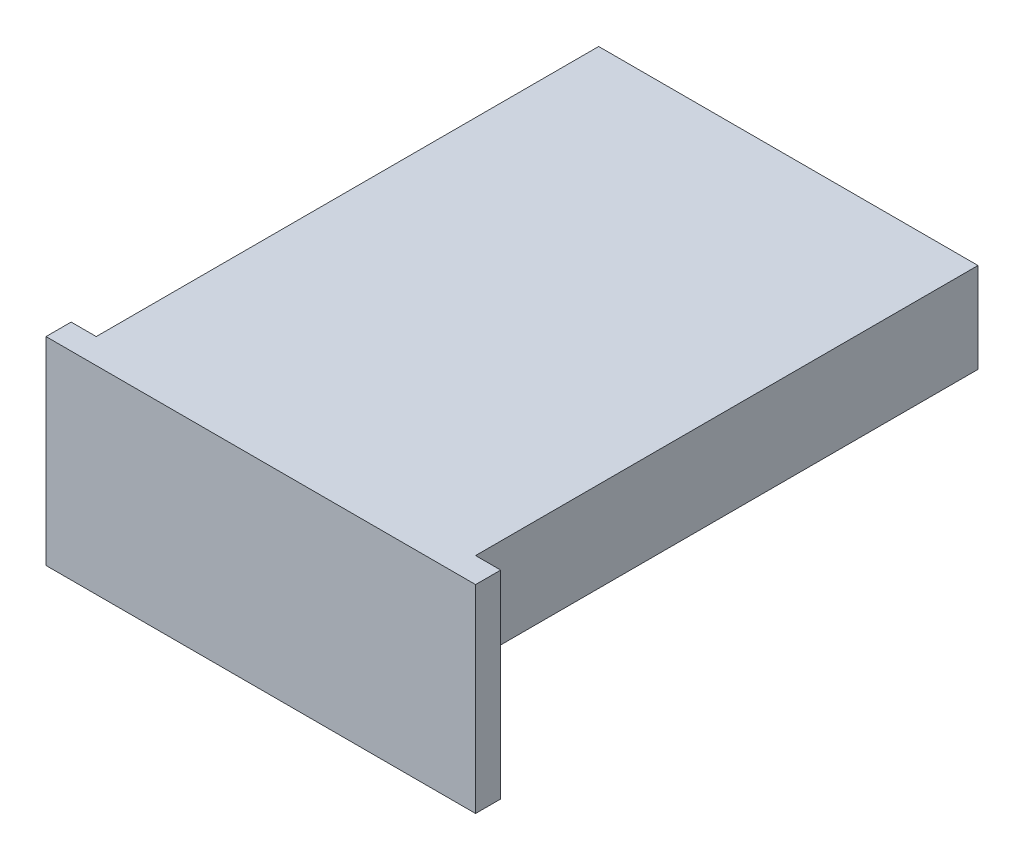
SolidWorks part; units mm, degrees
ref_plane "Front Plane" through (0, 0, 0) normal (0, 0, 1) x (1, 0, 0)
ref_plane "Top Plane" through (0, 0, 0) normal (0, 1, 0) x (1, 0, 0)
ref_plane "Right Plane" through (0, 0, 0) normal (1, 0, 0) x (0, 0, -1)
sketch "Sketch1" plane through (0, -22.4385, -0.0002) normal (0, 1, 0) x (1, 0, 0)
  line L4 (80.038, 6.103) -> (78.038, 6.103)
  line L5 (80.038, 6.103) -> (78.038, 6.103)
  line L6 (78.038, 26.103) -> (62.938, 26.103)
  line L7 (78.038, 26.103) -> (62.938, 26.103)
  line L14 (78.038, 6.103) -> (78.038, 26.103)
  line L15 (78.038, 6.103) -> (78.038, 26.103)
  line L16 (62.938, 26.103) -> (62.938, 6.103)
  line L17 (62.938, 26.103) -> (62.938, 6.103)
  line L79 (62.938, 6.103) -> (60.5428, 6.103)
  line L80 (62.938, 6.103) -> (60.5428, 6.103)
  line L81 (146.4404, 6.103) -> (146.4404, 26.103)
  line L82 (146.4404, 6.103) -> (146.4404, 26.103)
  line L83 (146.4404, 26.103) -> (131.338, 26.103)
  line L84 (146.4404, 26.103) -> (131.338, 26.103)
  line L85 (131.338, 26.103) -> (131.338, 6.103)
  line L86 (131.338, 26.103) -> (131.338, 6.103)
  line L87 (131.338, 6.103) -> (129.338, 6.103)
  line L88 (131.338, 6.103) -> (129.338, 6.103)
  line L89 (129.338, 6.103) -> (129.338, 26.103)
  line L90 (129.338, 6.103) -> (129.338, 26.103)
  line L91 (129.338, 26.103) -> (114.238, 26.103)
  line L92 (129.338, 26.103) -> (114.238, 26.103)
  line L93 (114.238, 26.103) -> (114.238, 6.103)
  line L94 (114.238, 26.103) -> (114.238, 6.103)
  line L95 (114.238, 6.103) -> (112.238, 6.103)
  line L96 (114.238, 6.103) -> (112.238, 6.103)
  line L97 (112.238, 6.103) -> (112.238, 26.103)
  line L98 (112.238, 6.103) -> (112.238, 26.103)
  line L99 (112.238, 26.103) -> (97.138, 26.103)
  line L100 (112.238, 26.103) -> (97.138, 26.103)
  line L101 (97.138, 26.103) -> (97.138, 6.103)
  line L102 (97.138, 26.103) -> (97.138, 6.103)
  line L103 (97.138, 6.103) -> (95.138, 6.103)
  line L104 (97.138, 6.103) -> (95.138, 6.103)
  line L105 (95.138, 6.103) -> (95.138, 26.103)
  line L106 (95.138, 6.103) -> (95.138, 26.103)
  line L107 (95.138, 26.103) -> (80.038, 26.103)
  line L108 (95.138, 26.103) -> (80.038, 26.103)
  line L109 (80.038, 26.103) -> (80.038, 6.103)
  line L110 (80.038, 26.103) -> (80.038, 6.103)
  line L111 (149.0321, 6.103) -> (146.4404, 6.103)
  line L112 (149.0321, 6.103) -> (146.4404, 6.103)
  arc A1 (60.5428, 6.103) -> (60.5959, 6.0115) centre (73.6219, 13.6322) ccw
  arc A2 (60.5428, 6.103) -> (60.5959, 6.0115) centre (73.6219, 13.6322) ccw
  spline S3 degree 3 poles (1817.8665, 957.8692) (-1812.7007, -801.1687) (1972.7377, 742.4675) (-1779.9076, -773.9188) knots -29.662381 -29.662381 -29.662381 -29.662381 32.998383 32.998383 32.998383 32.998383 only from (61.1644, 5.1151) to (62.5644, 3.3076)
  spline S4 degree 3 poles (548.8295, -1936.4915) (68.1721, 117.1489) (41.7438, 23.7507) (63.9834, 1.8165) (64.3645, 1.4758) (65.5511, 0.508) (66.3975, -0.0681) (68.1618, -1.131) (69.0656, -1.6129) (70.9072, -2.4757) (71.8473, -2.8546) (73.758, -3.5302) (74.728, -3.8283) (76.6807, -4.3902) (77.6629, -4.6553) (79.6355, -5.163) (80.6269, -5.4019) (82.6154, -5.8388) (83.6137, -6.0359) (85.6141, -6.4083) (86.6163, -6.584) (88.622, -6.928) (89.6256, -7.0959) (92.6392, -7.5851) (94.6533, -7.8906) (97.6787, -8.2804) (98.6882, -8.3974) (100.712, -8.5681) (101.7263, -8.6231) (103.759, -8.6779) (104.7772, -8.6815) (106.8164, -8.6518) (107.8346, -8.6197) (109.8636, -8.4895) (110.8742, -8.3881) (112.8914, -8.1479) (113.898, -8.0094) (116.9153, -7.5695) (118.9237, -7.2381) (121.9279, -6.7189) (122.9282, -6.542) (124.9259, -6.1777) (125.9229, -5.9891) (127.9067, -5.5749) (128.8931, -5.3485) (130.8559, -4.8592) (131.8333, -4.6003) (133.7815, -4.0591) (134.7528, -3.7785) (136.6775, -3.1531) (137.6304, -2.8065) (139.0374, -2.2069) (139.5031, -1.9951) (140.4295, -1.554) (140.891, -1.3271) (141.8041, -0.8385) (142.2585, -0.5733) (143.1225, 0.0059) (143.536, 0.3177) (144.1477, 0.7954) (144.3502, 0.9564) (144.7554, 1.2781) (144.9578, 1.4391) (162.9576, 16.0958) (166.0883, 48.1369) (-1083.6442, 1578.9651) knots -0.820445 -0.820445 -0.820445 -0.820445 0.115071 0.115071 0.130696 0.130696 0.161946 0.161946 0.193196 0.193196 0.224446 0.224446 0.255696 0.255696 0.286946 0.286946 0.318196 0.318196 0.349446 0.349446 0.380696 0.380696 0.411946 0.411946 0.474446 0.474446 0.505696 0.505696 0.536946 0.536946 0.568196 0.568196 0.599446 0.599446 0.630696 0.630696 0.661946 0.661946 0.724446 0.724446 0.755696 0.755696 0.786946 0.786946 0.818196 0.818196 0.849446 0.849446 0.880696 0.880696 0.911946 0.911946 0.927571 0.927571 0.943196 0.943196 0.958821 0.958821 0.974446 0.974446 0.982259 0.982259 0.990071 0.990071 1.683487 1.683487 1.683487 1.683487 only from (62.5644, 3.3076) to (145.9103, 2.2401)
  spline S6 degree 3 poles (61.1644, 5.1151) (61.5972, 4.4806) (62.0704, 3.8809) (62.5644, 3.3076) knots 0 0 0 0 0.685452 0.685452 0.685452 0.685452 construction
  spline S7 degree 3 poles (62.5644, 3.3076) (62.9009, 2.9175) (63.2527, 2.5372) (63.9834, 1.8165) (64.3645, 1.4758) (65.5511, 0.508) (66.3975, -0.0681) (68.1618, -1.131) (69.0656, -1.6129) (70.9072, -2.4757) (71.8473, -2.8546) (73.758, -3.5302) (74.728, -3.8283) (76.6807, -4.3902) (77.6629, -4.6553) (79.6355, -5.163) (80.6269, -5.4019) (82.6154, -5.8388) (83.6137, -6.0359) (85.6141, -6.4083) (86.6163, -6.584) (88.622, -6.928) (89.6256, -7.0959) (92.6392, -7.5851) (94.6533, -7.8906) (97.6787, -8.2804) (98.6882, -8.3974) (100.712, -8.5681) (101.7263, -8.6231) (103.759, -8.6779) (104.7772, -8.6815) (106.8164, -8.6518) (107.8346, -8.6197) (109.8636, -8.4895) (110.8742, -8.3881) (112.8914, -8.1479) (113.898, -8.0094) (116.9153, -7.5695) (118.9237, -7.2381) (121.9279, -6.7189) (122.9282, -6.542) (124.9259, -6.1777) (125.9229, -5.9891) (127.9067, -5.5749) (128.8931, -5.3485) (130.8559, -4.8592) (131.8333, -4.6003) (133.7815, -4.0591) (134.7528, -3.7785) (136.6775, -3.1531) (137.6304, -2.8065) (139.0374, -2.2069) (139.5031, -1.9951) (140.4295, -1.554) (140.891, -1.3271) (141.8041, -0.8385) (142.2585, -0.5733) (143.1225, 0.0059) (143.536, 0.3177) (144.1477, 0.7954) (144.3502, 0.9564) (144.7554, 1.2781) (144.9578, 1.4391) (145.4132, 1.8099) (145.6651, 2.021) (145.9103, 2.2401) knots 0.099446 0.099446 0.099446 0.099446 0.115071 0.115071 0.130696 0.130696 0.161946 0.161946 0.193196 0.193196 0.224446 0.224446 0.255696 0.255696 0.286946 0.286946 0.318196 0.318196 0.349446 0.349446 0.380696 0.380696 0.411946 0.411946 0.474446 0.474446 0.505696 0.505696 0.536946 0.536946 0.568196 0.568196 0.599446 0.599446 0.630696 0.630696 0.661946 0.661946 0.724446 0.724446 0.755696 0.755696 0.786946 0.786946 0.818196 0.818196 0.849446 0.849446 0.880696 0.880696 0.911946 0.911946 0.927571 0.927571 0.943196 0.943196 0.958821 0.958821 0.974446 0.974446 0.982259 0.982259 0.990071 0.990071 1 1 1 1 construction
  spline S16 degree 3 poles (1372.6595, -1576.7465) (65.1848, 24.8122) (129.0525, -14.1517) (146.6971, 2.9872) (147.0468, 3.3764) (147.7131, 4.1895) (148.0276, 4.6072) (165.4719, 29.2726) (129.935, 85.2105) (-1517.3371, 1110.9512) knots -0.67008 -0.67008 -0.67008 -0.67008 0.055384 0.055384 0.071009 0.071009 0.086634 0.086634 0.976126 0.976126 0.976126 0.976126 only from (145.9103, 2.2401) to (149.0321, 6.103)
  spline S17 degree 3 poles (145.9103, 2.2401) (146.0509, 2.3658) (146.1894, 2.4941) (146.6971, 2.9872) (147.0468, 3.3764) (147.7131, 4.1895) (148.0276, 4.6072) (148.5757, 5.3822) (148.8117, 5.7379) (149.0321, 6.103) knots 0.049688 0.049688 0.049688 0.049688 0.055384 0.055384 0.071009 0.071009 0.086634 0.086634 0.099446 0.099446 0.099446 0.099446
  spline S46 degree 3 poles (1817.9148, 957.8926) (-1812.905, -801.2651) (1973.1102, 742.6193) (-1780.4368, -774.1326) knots -28.662659 -28.662659 -28.662659 -28.662659 34.001328 34.001328 34.001328 34.001328 only from (60.5959, 6.0115) to (61.1644, 5.1151)
  spline S47 degree 3 poles (60.5959, 6.0115) (60.7756, 5.7048) (60.9657, 5.4063) (61.1644, 5.1151) knots 0.685452 0.685452 0.685452 0.685452 1 1 1 1
  dimension "D1" = 0
sketch "Sketch3" plane through (0, 0.0002, -26.103) normal (0, 0, 1) x (1, 0, 0)
  line L1 (97.138, 49.3018) -> (112.238, 49.3018)
  line L2 (97.138, 49.3018) -> (97.138, 45.7197)
  line L3 (97.138, 45.7197) -> (112.238, 45.7197)
  line L4 (112.238, 49.3018) -> (112.238, 45.7197)
  line L6 (97.1381, 145.3715) -> (97.138, -22.4385) construction
  line L7 (112.2381, 145.3715) -> (112.238, -22.4385) construction
  dimension "D1" = 15.1
extrude "Boss-Extrude1" add sketch "Sketch3" along normal up to surface (20 mm away)
sketch "Sketch4" plane through (0, 0, -6.103) normal (0, 0, 1) x (1, 0, 0)
  line L1 (96.138, 49.3018) -> (113.238, 49.3018)
  line L2 (96.138, 49.3018) -> (96.138, 41.4088)
  line L3 (96.138, 41.4088) -> (113.238, 41.4088)
  line L4 (113.238, 49.3018) -> (113.238, 41.4088)
  line L5 (97.138, 49.3018) -> (112.238, 49.3018) construction
  line L6 (95.138, 37.5077) -> (97.138, 37.5077) construction
  line L7 (95.1381, 145.3715) -> (95.138, -22.4385) construction
  line L8 (97.1381, 145.3715) -> (97.138, -22.4385) construction
  line L9 (96.138, 37.5077) -> (96.138, 51.6023) construction
  line L10 (112.238, 37.5077) -> (114.238, 37.5077) construction
  line L11 (112.2381, 145.3715) -> (112.238, -22.4385) construction
  line L12 (114.2381, 145.3715) -> (114.238, -22.4385) construction
  line L13 (113.238, 37.5077) -> (113.238, 51.6023) construction
  point P22 (154.9837, 51.6023)
  point P23 (0, 0)
  point P24 (0, 0)
  point P25 (0, 0)
  point P26 (154.9755, 37.5077)
extrude "Boss-Extrude2" add sketch "Sketch4" along normal blind 1
